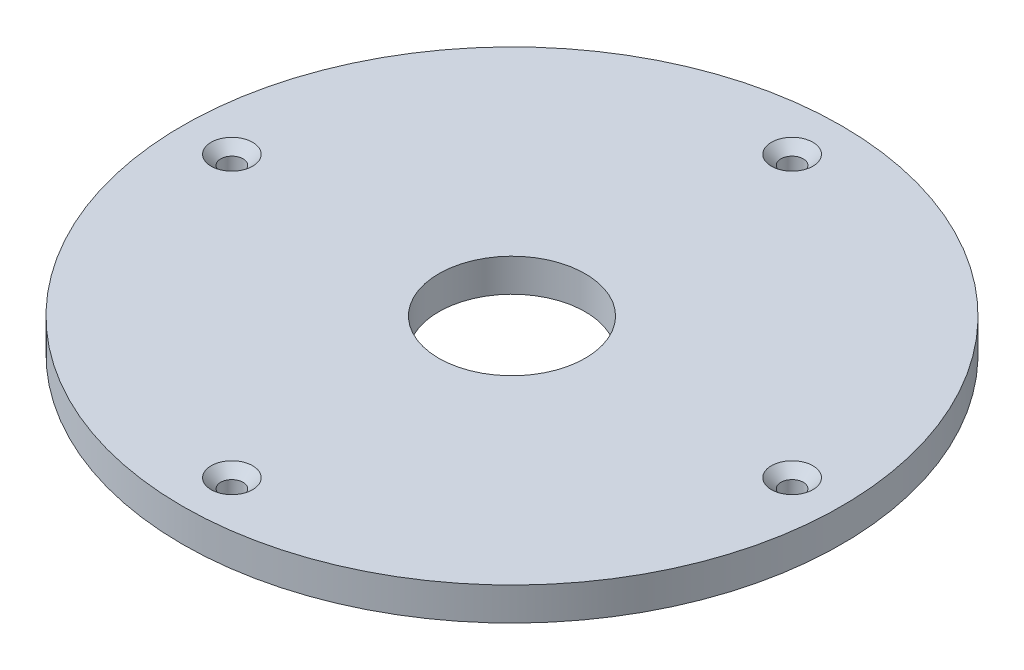
SolidWorks part; units mm, degrees
material "PE High Density"
ref_plane "Front Plane" through (0, 0, 0) normal (0, 0, 1) x (1, 0, 0)
ref_plane "Top Plane" through (0, 0, 0) normal (0, 1, 0) x (1, 0, 0)
ref_plane "Right Plane" through (0, 0, 0) normal (1, 0, 0) x (0, 0, -1)
sketch "Sketch1" plane through (0, 0, 0) normal (0, 1, 0) x (1, 0, 0)
  circle A0 centre (0, 0) radius 50
  circle A1 centre (0, 0) radius 11.1125
  point P0 (0, 42.5)
  dimension "D2" = 22.225
  dimension "D3" = 100
  dimension "D1" = 42.5
extrude "Boss-Extrude1" add sketch "Sketch1" along normal blind 5
sketch "Sketch2" plane through (0, 5, 0) normal (0, 1, 0) x (1, 0, 0)
  point P0 (0, 42.5)
hole_wizard "CSK for M3 Flat Head Machine Screw1" positions "Sketch2" profile "Sketch3" countersink size "M3" standard "ANSI Metric" end condition up to next
sketch "Sketch3" plane through (0, 5, -42.5) normal (1, 0, 0) x (0, 0, 1)
  line L0 (0, 0) -> (0, 5)
  line L1 (0, 5) -> (1.7, 5)
  line L2 (1.7, 5) -> (1.7, 1.45)
  line L3 (1.7, 1.45) -> (3.15, 0)
  line L5 (3.15, 0) -> (0, 0)
  line L6 (-1.7, 1.45) -> (-3.15, 0) construction
  line L11 (0, -6.35) -> (0, 107.95) construction
  dimension "Thru Hole Dia." = 3.4
  dimension "Thru Hole Depth" = 5
  dimension "Near C'Sink Dia." = 6.3
  dimension "Near C'Sink Angle" = 90
pattern_circular "CirPattern1" count 4 every 90 about axis through (0, 5, 0) along (0, -1, 0) of "CSK for M3 Flat Head Machine Screw1"
chamfer "Chamfer1" [suppressed] distance 2 angle 45
